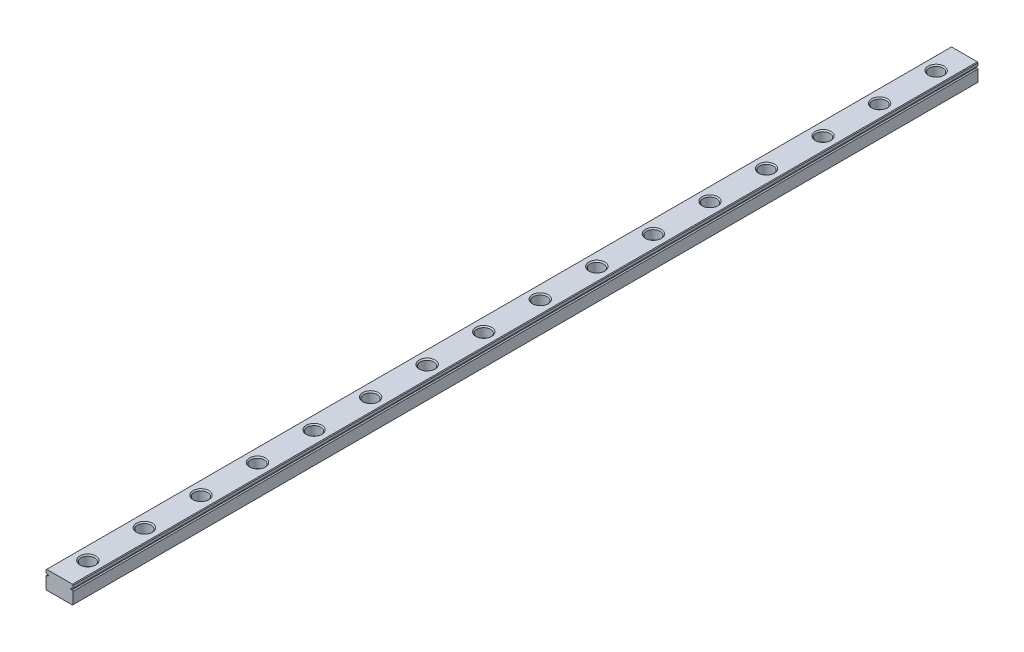
SolidWorks part; units mm, degrees
material "AISI 1045 鋼，冷拉"
ref_plane "Front Plane" through (0, 0, 0) normal (0, 0, 1) x (1, 0, 0)
ref_plane "Top Plane" through (0, 0, 0) normal (0, 1, 0) x (1, 0, 0)
ref_plane "Right Plane" through (0, 0, 0) normal (1, 0, 0) x (0, 0, -1)
sketch "Sketch1" plane through (0, 0, 0) normal (0, 0, 1) x (1, 0, 0)
  line L0 (-6, -4) -> (-6, 4) construction
  line L1 (-6, 4) -> (6, 4)
  line L2 (-6, -4) -> (6, -4)
  line L3 (-6, 4) -> (-6, 2.75)
  line L4 (-6, 2.75) -> (-5.5, 2.25) construction
  line L5 (-5.5, 2.25) -> (-5, 2.25)
  line L6 (-5.5, 1.75) -> (-6, 1.25) construction
  line L7 (-6, 1.25) -> (-6, -4)
  line L8 (-5, 2.25) -> (-5, 1.75)
  line L9 (-5, 1.75) -> (-5.5, 1.75)
  line L10 (-5.5, 1.75) -> (-5.25, 2) construction
  line L11 (-5.25, 2) -> (-5.5, 2.25) construction
  line L12 (-6, 2.75) -> (-6, 2.559)
  line L13 (-6, 1.25) -> (-6, 1.441)
  line L14 (0, 4) -> (0, -4) construction
  line L15 (5.25, 2) -> (5.5, 2.25) construction
  line L16 (5.5, 1.75) -> (5.25, 2) construction
  line L17 (5.5, 1.75) -> (6, 1.25) construction
  line L18 (6, 2.75) -> (5.5, 2.25) construction
  line L19 (6, -4) -> (6, 4) construction
  line L20 (6, 1.25) -> (6, 1.441)
  line L21 (6, 2.75) -> (6, 2.559)
  line L22 (5, 1.75) -> (5.5, 1.75)
  line L23 (5, 2.25) -> (5, 1.75)
  line L24 (6, 1.25) -> (6, -4)
  line L25 (5.5, 2.25) -> (5, 2.25)
  line L26 (6, 4) -> (6, 2.75)
  arc A0 (-6, 1.441) -> (-5.5, 1.75) centre (-6, 2) ccw
  arc A1 (-5.5, 2.25) -> (-6, 2.559) centre (-6, 2) ccw
  arc A2 (5.5, 2.25) -> (6, 2.559) centre (6, 2) cw
  arc A3 (6, 1.441) -> (5.5, 1.75) centre (6, 2) cw
  point P4 (-5, 2)
  point P28 (5, 2)
  dimension "D1" = 8
  dimension "D2" = 6
  dimension "D3" = 0.5
  dimension "D4" = 45
  dimension "D5" = 2
  dimension "D6" = 1
extrude "Boss-Extrude1" add sketch "Sketch1" along normal blind 400
chamfer "Chamfer1" distance 0.3 angle 45 4 edges at (-6, -4, 200) (6, -4, 200) (-6, 4, 200) (6, 4, 200)
hole_wizard "M3 六角承窩頭蓋螺釘的柱孔1" positions "3DSketch1" profile "Sketch3" counterbore size "M3" standard "ISO" end condition through all
sketch3d "3DSketch1"
  line L0 (0, 4, 0) -> (0, 4, 12.5) construction
  line L1 (5.7, 4, 0) -> (-5.7, 4, 0) construction
  point P0 (0, 4, 12.5)
  dimension "D1" = 12.5
sketch "Sketch3" plane through (0, 4, 12.5) normal (1, 0, 0) x (0, 0, 1)
  line L0 (0, 0) -> (0, 8)
  line L1 (1.75, 7.75) -> (2, 8)
  line L2 (3, 4.5) -> (1.75, 4.5)
  line L3 (1.75, 4.5) -> (1.75, 7.75)
  line L5 (3, 4.5) -> (3, 0.5)
  line L6 (3, 0.5) -> (3.5, 0)
  line L7 (3.5, 0) -> (0, 0)
  line L8 (-3, 0.5) -> (-3.5, 0) construction
  line L11 (0, -6.35) -> (0, 107.95) construction
  line L12 (2, 8) -> (0, 8)
  line L13 (-1.75, 7.75) -> (-2, 8) construction
  dimension "Thru Hole Dia." = 3.5
  dimension "Thru Hole Depth" = 8
  dimension "C'Bore Dia." = 6
  dimension "C'Bore Depth" = 4.5
  dimension "Near C'Sink Dia." = 7
  dimension "Near C'Sink Angle" = 90
  dimension "Far C'Sink Dia." = 4
  dimension "Far C'Sink Angle" = 90
pattern_linear "LPattern1" count 16 spacing 25 along (0, 0, 1) of "M3 六角承窩頭蓋螺釘的柱孔1"
